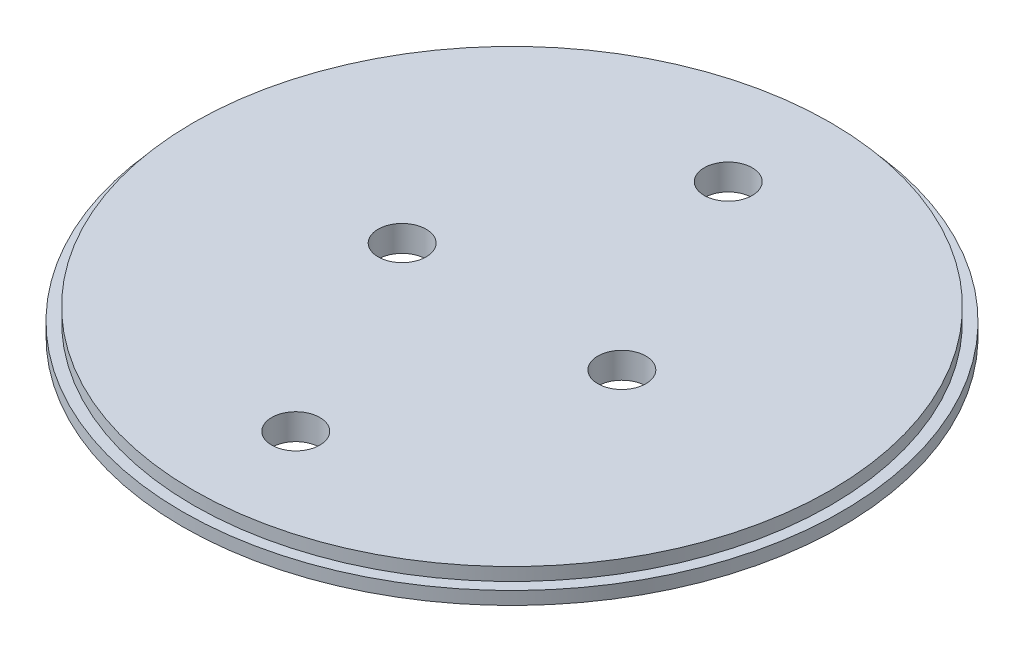
SolidWorks part; units mm, degrees
ref_plane "Front Plane" through (0, 0, 0) normal (0, 0, 1) x (1, 0, 0)
ref_plane "Top Plane" through (0, 0, 0) normal (0, 1, 0) x (1, 0, 0)
ref_plane "Right Plane" through (0, 0, 0) normal (1, 0, 0) x (0, 0, -1)
sketch "Sketch1" plane through (0, 0, 0) normal (0, 1, 0) x (1, 0, 0)
  line L0 (0, 0) -> (0, 50) construction
  line L1 (0, 0) -> (0, -50) construction
  line L2 (0, 0) -> (25.4, 0) construction
  line L3 (0, 0) -> (-25.4, 0) construction
  circle A0 centre (0, 0) radius 76.2
  circle A1 centre (0, 0) radius 73.65
  circle A2 centre (0, -50) radius 5.5563
  circle A3 centre (0, 50) radius 5.5563
  circle A4 centre (-25.4, 0) radius 5.5562
  circle A5 centre (25.4, 0) radius 5.5562
  dimension "D1" = 152.4
  dimension "D2" = 147.3
  dimension "D4" = 11.1125
  dimension "D3" = 100
  dimension "D5" = 50.8
extrude "Boss-Extrude1" add sketch "Sketch1" along normal blind 3 contours A1 A5 A4 A3 A2 region at (0, 0, 0)
extrude "Boss-Extrude2" add sketch "Sketch1<3>" against normal blind 3 contours A1 A5 A4 A3 A2 | A0 A1 region at (-74.0447, 0, 0) region at (0, 0, 0)
sketch "Sketch1<3>" plane through (0, 0, 0) normal (0, 1, 0) x (1, 0, 0) same geometry as "Sketch1"
